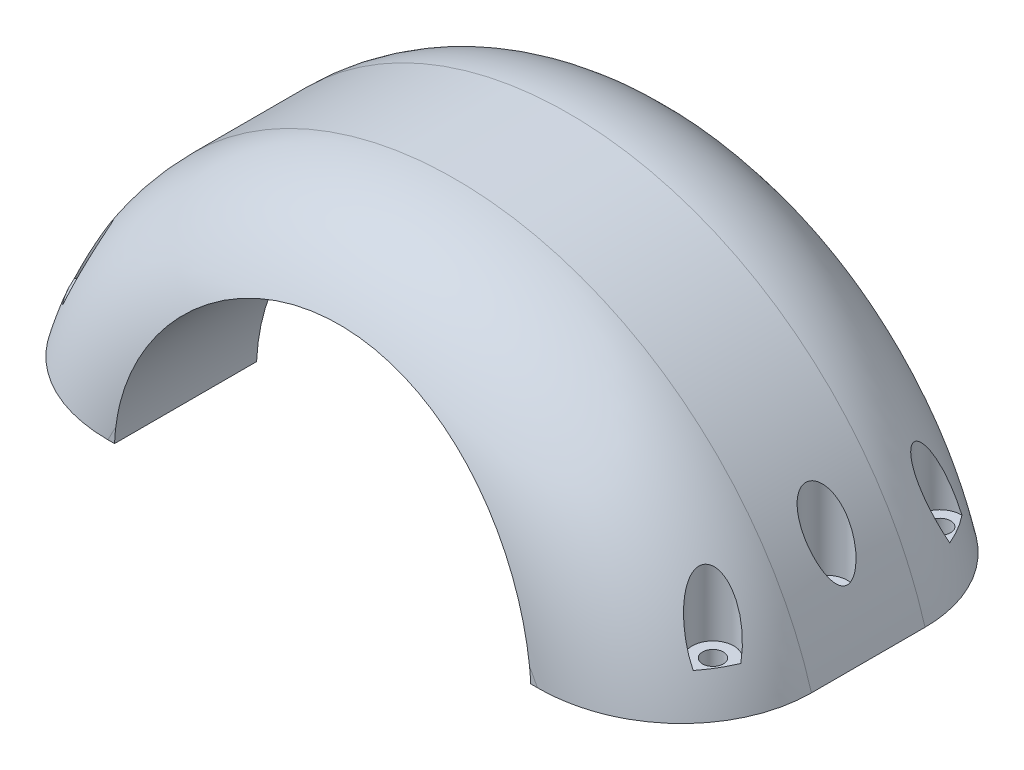
SolidWorks part; units mm, degrees
ref_plane "Front Plane" through (0, 0, 0) normal (0, 0, 1) x (1, 0, 0)
ref_plane "Top Plane" through (0, 0, 0) normal (0, 1, 0) x (1, 0, 0)
ref_plane "Right Plane" through (0, 0, 0) normal (1, 0, 0) x (0, 0, -1)
sketch "Sketch3" plane through (0, 0, 0) normal (0, 0, 1) x (1, 0, 0)
  line L0 (-94.0625, 2.5) -> (-54.9432, 2.5)
  line L2 (54.9432, 2.5) -> (94.0625, 2.5)
  arc A1 (94.0625, 2.5) -> (-94.0625, 2.5) centre (0, -25) ccw
  arc A2 (54.9432, 2.5) -> (-54.9432, 2.5) centre (0, 0) ccw
  point P3 (0, 55)
  point P4 (0, -25)
  point P13 (0, 73)
  dimension "D1" = 55
  dimension "D5" = 0
  dimension "D2" = 18
  dimension "D6" = 25
  dimension "D7" = 2.5
extrude "Boss-Extrude1" add sketch "Sketch3" along normal blind 100
ref_plane "Plane1" through (0, 0, 50) normal (0, 0, 1) x (1, 0, 0)
sketch "Sketch4" plane through (0, 0, 50) normal (0, 0, 1) x (1, 0, 0)
  line L2 (54.9432, 2.5) -> (94.0625, 2.5) construction
  line L3 (54.9432, 2.5) -> (69.9553, 2.5)
  line L4 (-54.9432, 2.5) -> (-69.9553, 2.5)
  arc A0 (-54.9432, 2.5) -> (54.9432, 2.5) centre (0, 0) cw
  arc A2 (-69.9553, 2.5) -> (69.9553, 2.5) centre (0, 0) cw
  dimension "D1" = 70
extrude "Cut-Extrude1" cut sketch "Sketch4" against normal mid plane 25 contours A2 L3 A0 L4
fillet "Fillet1" radius 35 1 edges at (0, 73, 0) type face fillet first side face at (0, 33.25, 0) second side face at (0, 37.75, 50)
fillet "Fillet2" radius 35 1 edges at (0, 73, 100) type face fillet first side face at (0, 33.25, 100) second side face at (0, 37.75, 67.5)
sketch "Sketch5" plane through (0, 2.5, 0) normal (0, -1, 0) x (1, 0, 0)
  line L0 (54.9432, 100) -> (56.6811, 100) construction
  line L1 (54.9432, 0) -> (56.6811, 0) construction
  line L2 (94.0625, 65) -> (94.0625, 35) construction
  circle A0 centre (83.0625, 80) radius 2.75
  circle A1 centre (83.0625, 50) radius 2.75
  circle A2 centre (83.0625, 20) radius 2.75
  dimension "D1" = 20
  dimension "D5" = 5.5
  dimension "D6" = 5.5
  dimension "D7" = 5.5
  dimension "D2" = 20
  dimension "D3" = 30
  dimension "D4" = 11
extrude "Cut-Extrude2" cut sketch "Sketch5" against normal blind 10
sketch "Sketch6" plane through (0, 12.5, 0) normal (0, -1, 0) x (1, 0, 0)
  circle A0 centre (83.0625, 20) radius 5.5
  circle A1 centre (83.0625, 50) radius 5.5
  circle A2 centre (83.0625, 80) radius 5.5
  dimension "D1" = 11
  dimension "D2" = 11
  dimension "D3" = 11
extrude "Cut-Extrude3" cut sketch "Sketch6" against normal through all
mirror "Mirror6" about plane through (0, 0, 0) normal (1, 0, 0) of "Cut-Extrude3", "Cut-Extrude2"
